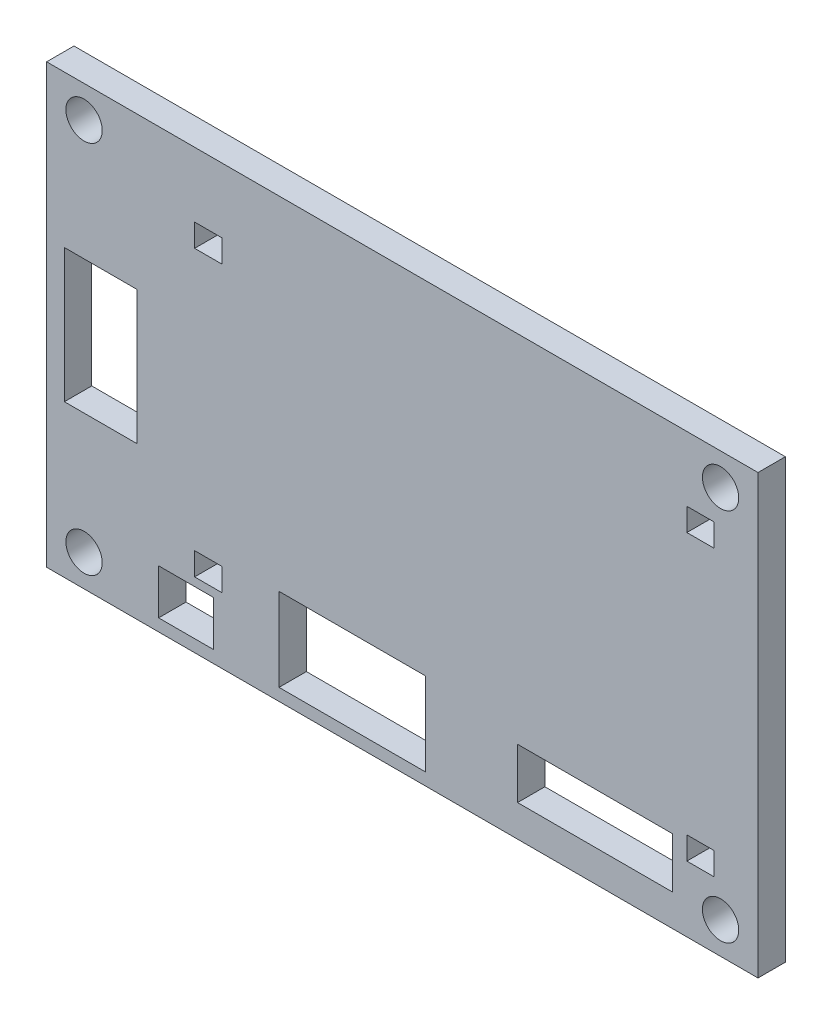
SolidWorks part; units mm, degrees
material "Beech"
ref_plane "Front Plane" through (0, 0, 0) normal (0, 0, 1) x (1, 0, 0)
ref_plane "Top Plane" through (0, 0, 0) normal (0, 1, 0) x (1, 0, 0)
ref_plane "Right Plane" through (0, 0, 0) normal (1, 0, 0) x (0, 0, -1)
sketch "Sketch1" plane through (0, 0, 0) normal (0, 0, 1) x (1, 0, 0)
  line L0 (-20.6375, 0) -> (20.6375, 0)
  line L44 (0, 14.605) -> (0, 24.13) construction
  line L46 (-20.6375, 0) -> (-20.6375, 25.4)
  line L47 (-20.6375, 25.4) -> (20.6375, 25.4)
  line L48 (20.6375, 0) -> (20.6375, 25.4)
  line L49 (-20.6375, 12.7) -> (20.6375, 12.7) construction
  circle A2 centre (-18.4658, 23.5585) radius 1.0541
  circle A3 centre (-18.4658, 1.8415) radius 1.0541
  circle A4 centre (18.4658, 1.8415) radius 1.0541
  circle A5 centre (18.4658, 23.5585) radius 1.0541
  point P0 (0, 0)
  point P56 (0, 12.7)
  point P60 (0, 25.4)
  dimension "D14" = 12.7
  dimension "D4" = 2.1082
  dimension "D3" = 25.4
  dimension "D12" = 41.275
  dimension "D5" = 2.1717
  dimension "D6" = 1.8415
extrude "Boss-Extrude1" add sketch "Sketch1" along normal blind 1.5875 contours L48 L47 L46 region at (0, 12.7, 0)
fillet "Fillet7" [suppressed] radius 15.24
sketch "Sketch2" plane through (0, 0, 1.5875) normal (0, 0, 1) x (1, 0, 0)
  line L0 (16.51, 20.32) -> (16.51, 21.6408) construction
  line L1 (16.51, 21.6408) -> (18.0975, 21.6408) construction
  line L2 (18.0975, 21.6408) -> (18.0975, 20.32) construction
  line L3 (18.0975, 20.32) -> (16.51, 20.32) construction
  line L4 (6.6858, 1.8395) -> (15.6858, 1.8395)
  line L5 (6.6858, 4.7695) -> (6.6858, 1.8395)
  line L6 (15.6858, 4.7695) -> (6.6858, 4.7695)
  line L7 (15.6858, 1.8395) -> (15.6858, 4.7695)
  line L8 (6.6858, 1.8395) -> (15.6858, 1.8395)
  line L9 (6.6858, 4.7695) -> (6.6858, 1.8395)
  line L10 (15.6858, 4.7695) -> (6.6858, 4.7695)
  line L11 (15.6858, 1.8395) -> (15.6858, 4.7695)
  line L12 (1.3552, 5.5335) -> (-7.1538, 5.5335)
  line L13 (1.3552, 0.7075) -> (1.3552, 5.5335)
  line L14 (-7.1538, 0.7075) -> (1.3552, 0.7075)
  line L15 (-7.1538, 5.5335) -> (-7.1538, 0.7075)
  line L16 (1.3552, 5.5335) -> (-7.1538, 5.5335)
  line L17 (1.3552, 0.7075) -> (1.3552, 5.5335)
  line L18 (-7.1538, 0.7075) -> (1.3552, 0.7075)
  line L19 (-7.1538, 5.5335) -> (-7.1538, 0.7075)
  line L20 (-10.9638, 3.3237) -> (-14.1388, 3.3237)
  line L21 (-10.9638, 0.7075) -> (-10.9638, 3.3237)
  line L22 (-14.1388, 0.7075) -> (-10.9638, 0.7075)
  line L23 (-14.1388, 3.3237) -> (-14.1388, 0.7075)
  line L24 (-10.9638, 3.3237) -> (-14.1388, 3.3237)
  line L25 (-10.9638, 0.7075) -> (-10.9638, 3.3237)
  line L26 (-14.1388, 0.7075) -> (-10.9638, 0.7075)
  line L27 (-14.1388, 3.3237) -> (-14.1388, 0.7075)
  line L28 (-19.6078, 8.834) -> (-15.3878, 8.834)
  line L29 (-19.6078, 16.584) -> (-19.6078, 8.834)
  line L30 (-15.3878, 16.584) -> (-19.6078, 16.584)
  line L31 (-15.3878, 8.834) -> (-15.3878, 16.584)
  line L32 (-19.6078, 8.834) -> (-15.3878, 8.834)
  line L33 (-19.6078, 16.584) -> (-19.6078, 8.834)
  line L34 (-15.3878, 16.584) -> (-19.6078, 16.584)
  line L35 (-15.3878, 8.834) -> (-15.3878, 16.584)
  line L36 (16.51, 3.81) -> (16.51, 5.1308) construction
  line L37 (16.51, 5.1308) -> (18.0975, 5.1308) construction
  line L38 (18.0975, 5.1308) -> (18.0975, 3.81) construction
  line L39 (18.0975, 3.81) -> (16.51, 3.81) construction
  line L40 (-12.0523, 3.81) -> (-12.0523, 5.1308) construction
  line L41 (-12.0523, 5.1308) -> (-10.4648, 5.1308) construction
  line L42 (-10.4648, 5.1308) -> (-10.4648, 3.81) construction
  line L43 (-10.4648, 3.81) -> (-12.0523, 3.81) construction
  line L44 (-12.0523, 20.32) -> (-12.0523, 21.6408) construction
  line L45 (-12.0523, 21.6408) -> (-10.4648, 21.6408) construction
  line L46 (-10.4648, 21.6408) -> (-10.4648, 20.32) construction
  line L47 (-10.4648, 20.32) -> (-12.0523, 20.32) construction
  line L48 (16.51, 20.32) -> (16.51, 21.6408)
  line L49 (16.51, 21.6408) -> (18.0975, 21.6408)
  line L50 (18.0975, 21.6408) -> (18.0975, 20.32)
  line L51 (18.0975, 20.32) -> (16.51, 20.32)
  line L52 (16.51, 3.81) -> (16.51, 5.1308)
  line L53 (16.51, 5.1308) -> (18.0975, 5.1308)
  line L54 (18.0975, 5.1308) -> (18.0975, 3.81)
  line L55 (18.0975, 3.81) -> (16.51, 3.81)
  line L56 (-12.0523, 3.81) -> (-12.0523, 5.1308)
  line L57 (-12.0523, 5.1308) -> (-10.4648, 5.1308)
  line L58 (-10.4648, 5.1308) -> (-10.4648, 3.81)
  line L59 (-10.4648, 3.81) -> (-12.0523, 3.81)
  line L60 (-12.0523, 20.32) -> (-12.0523, 21.6408)
  line L61 (-12.0523, 21.6408) -> (-10.4648, 21.6408)
  line L62 (-10.4648, 21.6408) -> (-10.4648, 20.32)
  line L63 (-10.4648, 20.32) -> (-12.0523, 20.32)
  dimension "D1" = 0
  dimension "D2" = 0
  dimension "D3" = 0
  dimension "D4" = 0
extrude "Cut-Extrude1" cut sketch "Sketch2" against normal up to surface (1.5875 mm away) up to face at (-17.4117, 1.8415, 0)
move or copy body "Body-Move/Copy1" [suppressed] bodies to move or copy 105
